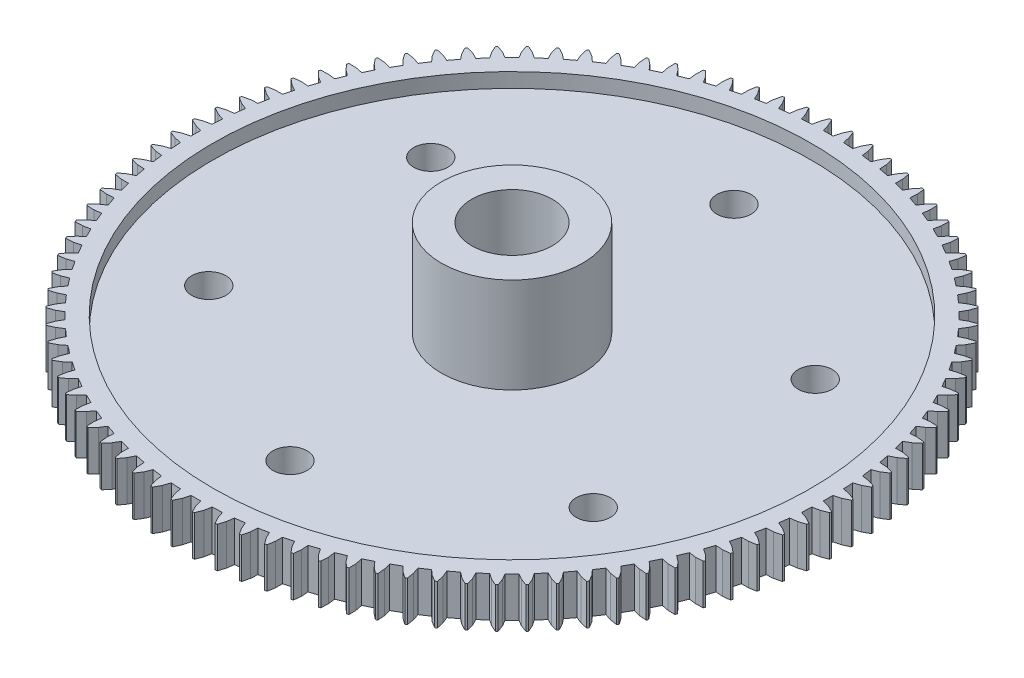
SolidWorks part; units mm, degrees
ref_plane "Front Plane" through (0, 0, 0) normal (0, 0, 1) x (1, 0, 0)
ref_plane "Top Plane" through (0, 0, 0) normal (0, 1, 0) x (1, 0, 0)
ref_plane "Right Plane" through (0, 0, 0) normal (1, 0, 0) x (0, 0, -1)
sketch "Sketch1" plane through (0, 0, 0) normal (0, 1, 0) x (1, 0, 0)
  circle A0 centre (0, 0) radius 25.9334
  dimension "D1" = 51.8668
extrude "Boss-Extrude1" add sketch "Sketch1" along normal blind 3.175
sketch "Sketch2" plane through (0, 3.175, 0) normal (0, 1, 0) x (1, 0, 0)
  circle A0 centre (0, 0) radius 5.5499
  dimension "D1" = 11.0998
extrude "Boss-Extrude2" add sketch "Sketch2" along normal blind 6.35
sketch "Sketch3" plane through (0, 9.525, 0) normal (0, 1, 0) x (1, 0, 0)
  circle A0 centre (0, 0) radius 3.175
  dimension "D1" = 6.35
extrude "Cut-Extrude1" cut sketch "Sketch3" against normal through all
sketch "Sketch4" plane through (0, 3.175, 0) normal (0, 1, 0) x (1, 0, 0)
  circle A0 centre (0, 0) radius 5.5499
  circle A1 centre (0, 0) radius 23.5204
  dimension "D1" = 47.0408
extrude "Cut-Extrude2" cut sketch "Sketch4" against normal blind 1.143
sketch "Sketch5" plane through (0, 3.175, 0) normal (0, 1, 0) x (1, 0, 0)
  line L0 (0, 0) -> (0, 45.2162) construction
  circle A0 centre (0, 17.4625) radius 1.3462
extrude "Cut-Extrude3" cut sketch "Sketch5" against normal through all
pattern_circular "CirPattern1" count 6 over 360 about axis through (0, 3.175, 0) along (0, -1, 0) of "Cut-Extrude3"
sketch "Sketch6" plane through (0, 3.175, 0) normal (0, 1, 0) x (1, 0, 0)
  line L0 (0, 0) -> (0, 25.4) construction
  line L1 (-0.5292, 25.4) -> (0.5292, 25.4) construction
  line L3 (-0.5292, 25.4) -> (-1.1384, 26.7066)
  line L4 (-1.1384, 26.7066) -> (1.1384, 26.7066)
  line L5 (1.1384, 26.7066) -> (0.5292, 25.4)
  line L6 (-0.5292, 25.4) -> (-0.3862, 24.8666)
  line L7 (0.5292, 25.4) -> (0.3862, 24.8666)
  line L8 (0.3862, 24.8666) -> (-0.3862, 24.8666)
  dimension "D1" = 115
  dimension "D2" = 115
  dimension "D3" = 75
  dimension "D4" = 75
extrude "Cut-Extrude4" cut sketch "Sketch6" against normal through all
pattern_circular "CirPattern2" count 96 over 360 about axis through (0, 3.175, 0) along (0, -1, 0) of "Cut-Extrude4"
